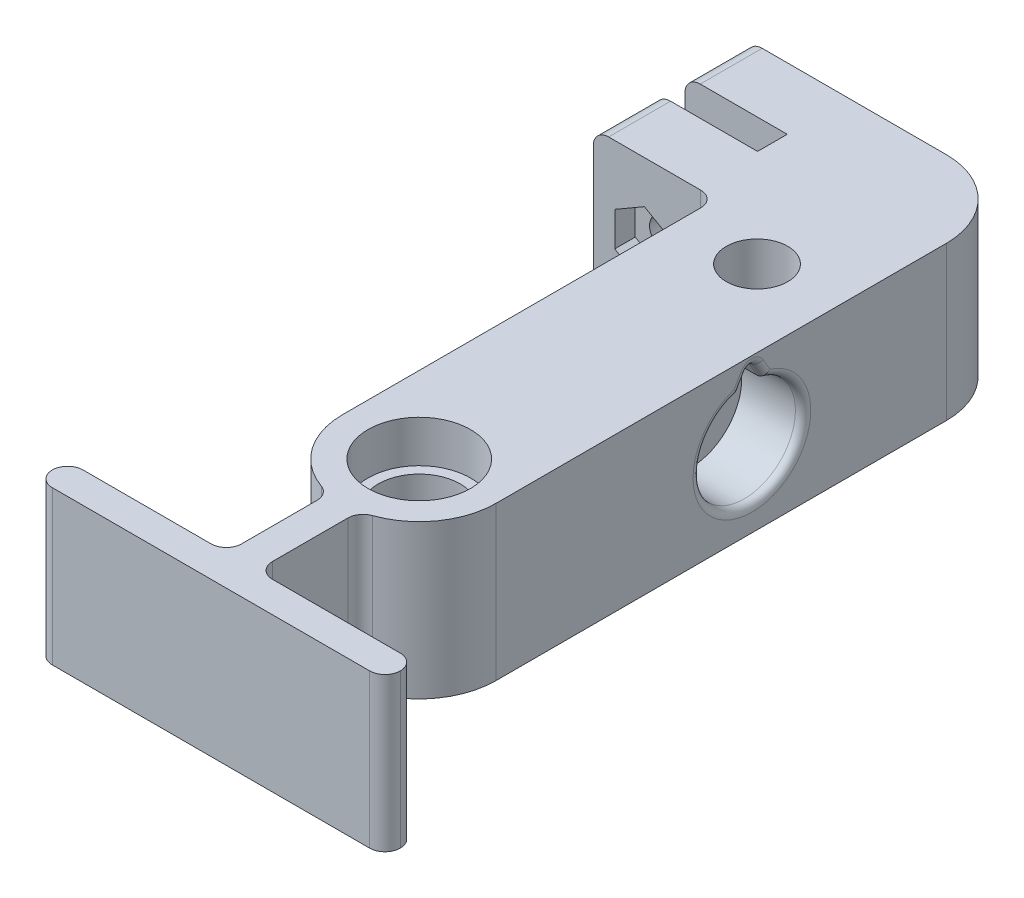
SolidWorks part; units mm, degrees
ref_plane "Front Plane" through (0, 0, 0) normal (0, 0, 1) x (1, 0, 0)
ref_plane "Top Plane" through (0, 0, 0) normal (0, 1, 0) x (1, 0, 0)
ref_plane "Right Plane" through (0, 0, 0) normal (1, 0, 0) x (0, 0, -1)
sketch "Sketch1" plane through (0, 0, 0) normal (0, 1, 0) x (1, 0, 0)
  line L0 (0, 22) -> (0, -22) construction
  line L1 (-7.5, 22) -> (7.5, 22)
  line L2 (-7.5, 22) -> (-7.5, -22)
  line L3 (-7.5, -22) -> (7.5, -22)
  line L4 (7.5, 22) -> (7.5, -22)
  line L5 (-7.5, 22) -> (7.5, -22) construction
  line L6 (-7.5, -22) -> (7.5, 22) construction
  circle A0 centre (0, -14.5) radius 4
  circle A1 centre (0, -14.5) radius 7.5
  point P0 (0, 0)
  dimension "D1" = 8
  dimension "D2" = 15
  dimension "D4" = 44
extrude "Boss-Extrude1" add sketch "Sketch1" along normal mid plane 15 contours L2 | L4 | A1 L4 L1 L2 | A1 A0 | L3 region at (0, 0, -6.6495) region at (0, 0, 7.2121)
sketch "Sketch2" plane through (0, 7.5, 0) normal (0, 1, 0) x (1, 0, 0)
  circle A0 centre (0, -14.5) radius 5
  dimension "D1" = 10
extrude "Cut-Extrude1" cut sketch "Sketch2" against normal blind 4.1
mirror "Mirror1" about plane through (0, 0, 0) normal (0, 1, 0) of "Cut-Extrude1"
sketch "Sketch12" plane through (0, -3.4, 0) normal (0, -1, 0) x (1, 0, 0)
  circle A0 centre (0, 14.5) radius 4 construction
  circle A1 centre (0, 14.5) radius 5
  circle A2 centre (0, 14.5) radius 5
  circle A3 centre (0, 14.5) radius 4
  dimension "D1" = 0
extrude "Cut-Extrude10" cut sketch "Sketch12" against normal blind 0.5
sketch "Sketch4" plane through (7.5, 0, 0) normal (1, 0, 0) x (0, 0, -1)
  line L0 (-3.1918, 0) -> (3.917, 0) construction
  line L1 (9.25, 4.8412) -> (11.75, 4.8412) construction
  line L2 (-9.5, 7.5) -> (-19.5, 7.5) construction
  line L3 (-9.5, 7.5) -> (-19.5, 7.5)
  line L4 (-14.5, 7.5) -> (-14.5, -7.5) construction
  line L5 (22, -7.5) -> (-14.5, -7.5) construction
  line L6 (10.5, 0) -> (10.5, 7.5) construction
  line L9 (22, 7.5) -> (-14.5, 7.5) construction
  line L10 (10.5, 7.0063) -> (9.25, 4.8412)
  line L11 (10.5, 7.0063) -> (11.75, 4.8412)
  circle A1 centre (10.5, 0) radius 5
  circle A3 centre (10.5, 6.0063) radius 0.5
  dimension "D1" = 25
  dimension "D2" = 10
  dimension "D5" = 1
  dimension "D4" = 2.5
extrude "Cut-Extrude3" cut sketch "Sketch4" against normal blind 6 contours A1 | A1 L11 L10 | A3 region at (7.5, 5.3219, -10.5) region at (7.5, 6.0063, -10.5) region at (7.5, 0, -10.5)
mirror "Mirror2" about plane through (0, 0, 0) normal (1, 0, 0) of "Cut-Extrude3"
sketch "Sketch18" plane through (0, -7.5, 0) normal (0, -1, 0) x (1, 0, 0)
  line L0 (0, -41.3409) -> (0, 22.3101) construction
  line L4 (7.5, -3.75) -> (-7.5, -3.75) construction
  line L5 (-19.5, -22) -> (-7.5, -22)
  line L6 (7.5, -29.5) -> (7.5, -22)
  line L7 (7.5, -22) -> (7.5, 14.5) construction
  line L8 (-7.5, -22) -> (7.5, -22)
  line L9 (-7.5, -22) -> (-7.5, 14.5) construction
  line L10 (0, -22) -> (0, -37) construction
  line L11 (0, -37) -> (-19.5, -37)
  line L13 (-19.5, -22) -> (-19.5, -37)
  circle A1 centre (0, -29.5) radius 7.5
  line M10 (-7.5, -22) -> (7.5, -22)
  dimension "D1" = 12
extrude "Boss-Extrude3" add sketch "Sketch18" against normal up to surface (15 mm away) contours A1 L6 L8 | A1 M10 | A1 | A1 L13 L11 region at (-12.5923, -7.5, -29.5) region at (5.8247, -7.5, -23.6753) region at (0, -7.5, -29.5) up to face at (0, 7.5, 19.5)
sketch "Sketch7" plane through (0, 7.5, 0) normal (0, 1, 0) x (1, 0, 0)
  line L0 (-19.5, 29.5) -> (7.5, 29.5) construction
  line L8 (7.5, 29.5) -> (7.5, -14.5) construction
  line L9 (-19.5, 28.05) -> (-9.5, 28.05)
  line L10 (-19.5, 28.05) -> (-19.5, 30.95)
  line L11 (-9.5, 28.05) -> (-9.5, 30.95)
  line L12 (-19.5, 30.95) -> (-9.5, 30.95)
  line L13 (-19.5, 28.05) -> (-9.5, 30.95) construction
  line L14 (-9.5, 28.05) -> (-19.5, 30.95) construction
  line L15 (-19.5, 22) -> (-19.5, 37) construction
  point P8 (-14.5, 29.5)
  dimension "D1" = 10
  dimension "D2" = 2.9
extrude "Cut-Extrude7" cut sketch "Sketch7" against normal up to next
sketch "Sketch8" plane through (-40.2452, 0, -37) normal (0, 0, 1) x (1, 0, 0)
  line L5 (20.7452, 0) -> (40.2452, 0) construction
  line L8 (20.7452, 7.5) -> (20.7452, -7.5) construction
  line L9 (40.2452, 7.5) -> (40.2452, -7.5) construction
  circle A2 centre (25.7452, 0) radius 1.5
  dimension "D2" = 5
  dimension "D3" = 3
extrude "Cut-Extrude8" cut sketch "Sketch8" along normal up to surface (15 mm away) contours A2
hole_wizard "CSK for M3 Flat Head Machine Screw1" positions "Sketch9" profile "Sketch10" countersink size "M3" standard "ANSI Metric"
sketch "Sketch9" plane through (-83.1458, 0, -37) normal (0, 0, 1) x (1, 0, 0)
  point P6 (68.6458, 0)
  point P17 (0, 0)
  point P18 (0, 0)
  point P19 (0, 0)
  point P20 (0, 0)
sketch "Sketch10" plane through (-14.5, 0, -37) normal (1, 0, 0) x (0, 1, 0)
  line L0 (0, 0) -> (0, 5.9013)
  line L1 (0, 5.9013) -> (1.5, 5)
  line L2 (1.5, 5) -> (1.5, 1.8)
  line L3 (1.5, 1.8) -> (3, 0.3)
  line L4 (3, 0.3) -> (3, 0)
  line L6 (3, 0) -> (0, 0)
  line L7 (-1.5, 1.8) -> (-3, 0.3) construction
  line L10 (0, 5.9013) -> (-1.5, 5) construction
  line L11 (0, -6.35) -> (0, 107.95) construction
  dimension "Hole Dia." = 3
  dimension "Hole Depth" = 5
  dimension "C'Sink Dia." = 6
  dimension "C'Sink Angle" = 90
  dimension "Drill Angle" = 118
  dimension "Head Clearance" = 0.3
sketch "Sketch11" plane through (15, 0, -22) normal (0, 0, 1) x (1, 0, 0)
  line L7 (-34.5, 7.5) -> (-34.5, -7.5) construction
  line L8 (-29.5, -3.3486) -> (-26.6, -1.6743)
  line L15 (-26.6, -1.6743) -> (-26.6, 1.6743)
  line L16 (-26.6, 1.6743) -> (-29.5, 3.3486)
  line L17 (-29.5, 3.3486) -> (-32.4, 1.6743)
  line L18 (-32.4, 1.6743) -> (-32.4, -1.6743)
  line L19 (-32.4, -1.6743) -> (-29.5, -3.3486)
  circle A0 centre (-29.5, 0) radius 2.9 construction
  dimension "D1" = 5.8
extrude "Cut-Extrude9" cut sketch "Sketch11" against normal blind 2
sketch "Sketch13" plane through (-44.6536, 0, -30.95) normal (0, 0, 1) x (1, 0, 0)
  line L0 (35.1536, -7.5) -> (35.1536, 7.5) construction
  line L2 (35.1536, -7.5) -> (35.1536, 7.5)
  line L3 (35.1536, 0) -> (44.6536, 0) construction
  line L4 (44.6536, 7.5) -> (44.6536, -7.5) construction
  line L5 (35.1536, 7.5) -> (42.6536, 0)
  line L6 (35.1536, -7.5) -> (42.6536, 0)
  dimension "D1" = 45
extrude "Cut-Extrude11" cut sketch "Sketch13" along normal up to surface (2.9 mm away) contours L5 L6 L2 up to face at (-13, 0, -28.05)
sketch "Sketch16" plane through (0, -7.5, 0) normal (0, -1, 0) x (1, 0, 0)
  line L0 (0, 42.718) -> (0, -5.4521) construction
  line L2 (-1.5, 31.8485) -> (1.5, 31.8485)
  line L3 (-1.5, 31.8485) -> (-1.5, 21.8485)
  line L4 (-1.5, 21.8485) -> (1.5, 21.8485)
  line L5 (1.5, 31.8485) -> (1.5, 21.8485)
  line L6 (-1.5, 31.8485) -> (1.5, 21.8485) construction
  line L7 (-1.5, 21.8485) -> (1.5, 31.8485) construction
  line L8 (-17, 34.8485) -> (17, 34.8485)
  line L9 (-17, 34.8485) -> (-17, 31.8485)
  line L10 (-17, 31.8485) -> (17, 31.8485)
  line L11 (17, 34.8485) -> (17, 31.8485)
  line L12 (-17, 34.8485) -> (17, 31.8485) construction
  line L13 (-17, 31.8485) -> (17, 34.8485) construction
  arc A0 (7.5, 14.5) -> (-7.5, 14.5) centre (0, 14.5) ccw construction
  point P1 (0, 26.8485)
  point P11 (0, 33.3485)
  arc M14 (7.5, 14.5) -> (-7.5, 14.5) centre (0, 14.5) ccw
  dimension "D1" = 3
  dimension "D2" = 10
  dimension "D3" = 34
extrude "Boss-Extrude2" add sketch "Sketch16" against normal up to surface (15 mm away) contours L5 L2 L3 M14 | L11 L8 L9 L10 L2 region at (0, -7.5, 33.3485) region at (0, -7.5, 26.899) up to face at (-8.677, 7.5, -20.9594)
fillet "Fillet8" radius 1.5 14 edges at (17, 0, 31.8485) (17, 0, 34.8485) (-17, 0, 34.8485) (-17, 0, 31.8485) (-1.5, 0, 31.8485) (-1.5, 0, 21.8485) (1.5, 0, 21.8485) (1.5, 0, 31.8485) (-19.5, -7.5, -25.025) (-19.5, -7.5, -33.975) (-19.5, 7.5, -33.975) (-19.5, 7.5, -25.025) (-7.5, 0, -22) (-2, 0, -29.5)
sketch "Sketch19" plane through (0, -7.5, 0) normal (0, -1, 0) x (1, 0, 0)
  line L0 (0, 4.3088) -> (0, -5.4508) construction
  circle A0 centre (0, -18.5) radius 3
  circle A2 centre (0, 14.5) radius 5 construction
  dimension "D1" = 6
  dimension "D2" = 33
extrude "Cut-Extrude12" cut sketch "Sketch19" against normal up to next contours A0
fillet "Fillet9" radius 0.75 8 edges at (-7.5, 5.5488, -11.3415) (-7.5, 6.5063, -10.5) (7.5, 5.5488, -9.6585) (7.5, 6.5063, -10.5) (-7.5, 5.5488, -9.6585) (-7.5, -5, -10.5) (7.5, 5.5488, -11.3415) (7.5, -5, -10.5)
